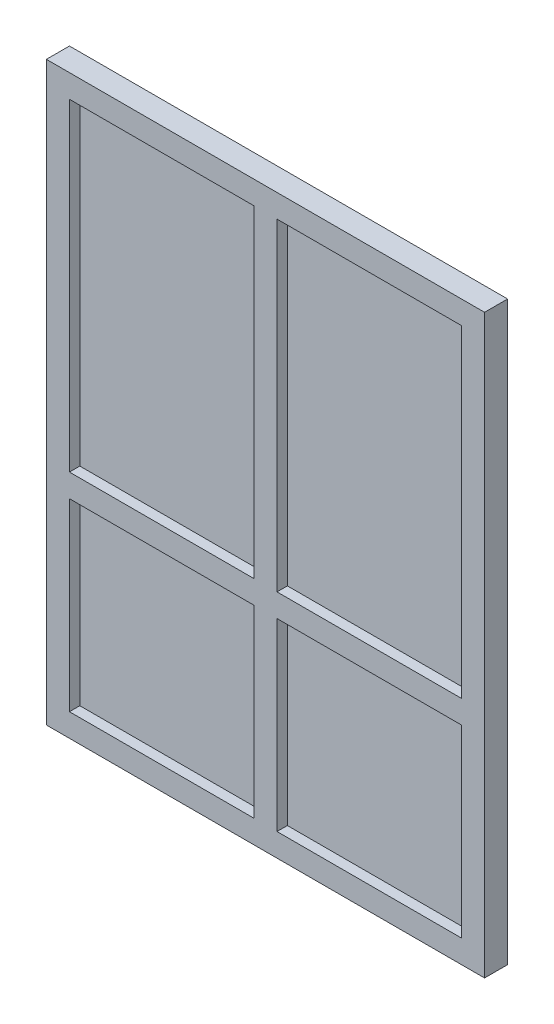
SolidWorks part; units mm, degrees
ref_plane "Спереди" through (0, 0, 0) normal (0, 0, 1) x (1, 0, 0)
ref_plane "Сверху" through (0, 0, 0) normal (0, 1, 0) x (1, 0, 0)
ref_plane "Справа" through (0, 0, 0) normal (1, 0, 0) x (0, 0, -1)
other "Configuration Table"
sketch "Эскиз1" plane through (0, 0, 0) normal (0, 0, 1) x (1, 0, 0)
  line L0 (0, 900) -> (100, 900) construction
  line L1 (-900, 2500) -> (1000, 2500)
  line L2 (-900, 2500) -> (-900, 0)
  line L3 (-900, 0) -> (1000, 0)
  line L4 (1000, 2500) -> (1000, 0)
  line L5 (-800, 2400) -> (0, 2400)
  line L6 (-800, 2400) -> (-800, 1000)
  line L7 (-800, 1000) -> (0, 1000)
  line L8 (0, 2400) -> (0, 1000)
  line L9 (-800, 900) -> (0, 900)
  line L10 (-800, 900) -> (-800, 100)
  line L11 (-800, 100) -> (0, 100)
  line L12 (0, 900) -> (0, 100)
  line L13 (100, 2400) -> (900, 2400)
  line L14 (100, 2400) -> (100, 1000)
  line L15 (100, 1000) -> (900, 1000)
  line L16 (900, 2400) -> (900, 1000)
  line L17 (100, 900) -> (900, 900)
  line L18 (100, 900) -> (100, 100)
  line L19 (100, 100) -> (900, 100)
  line L20 (900, 900) -> (900, 100)
  line L21 (100, 900) -> (100, 1000) construction
  line L22 (900, 900) -> (900, 1000) construction
  line L23 (-800, 900) -> (-800, 1000) construction
  line L24 (0, 900) -> (0, 1000) construction
  line L25 (0, 1000) -> (100, 1000) construction
  line L26 (0, 2400) -> (100, 2400) construction
  line L27 (0, 100) -> (100, 100) construction
  line L28 (-800, 2400) -> (-800, 2500) construction
  line L29 (-800, 2500) -> (-800, 2400) construction
  line L30 (-800, 100) -> (-800, 0) construction
  line L31 (-800, 2400) -> (-900, 2400) construction
  line L32 (900, 2400) -> (1000, 2400) construction
  line L34 (-900, 0) -> (1000, 0) construction
  line L35 (1000, 2500) -> (1000, 0) construction
  dimension "D1" = 100
  dimension "D2" = 1400
extrude "Бобышка-Вытянуть1" add sketch "Эскиз1" along normal mid plane 100
ref_plane "Плоскость1" through (0, 0, 0) normal (0, 0, 1) x (1, 0, 0)
sketch "Эскиз2" plane through (0, 0, 0) normal (0, 0, 1) x (1, 0, 0)
  line L1 (-800, 2400) -> (900, 2400)
  line L2 (-800, 2400) -> (-800, 100)
  line L3 (-800, 100) -> (900, 100)
  line L4 (900, 2400) -> (900, 100)
extrude "Бобышка-Вытянуть2" add sketch "Эскиз2" along normal mid plane 10 separate body
